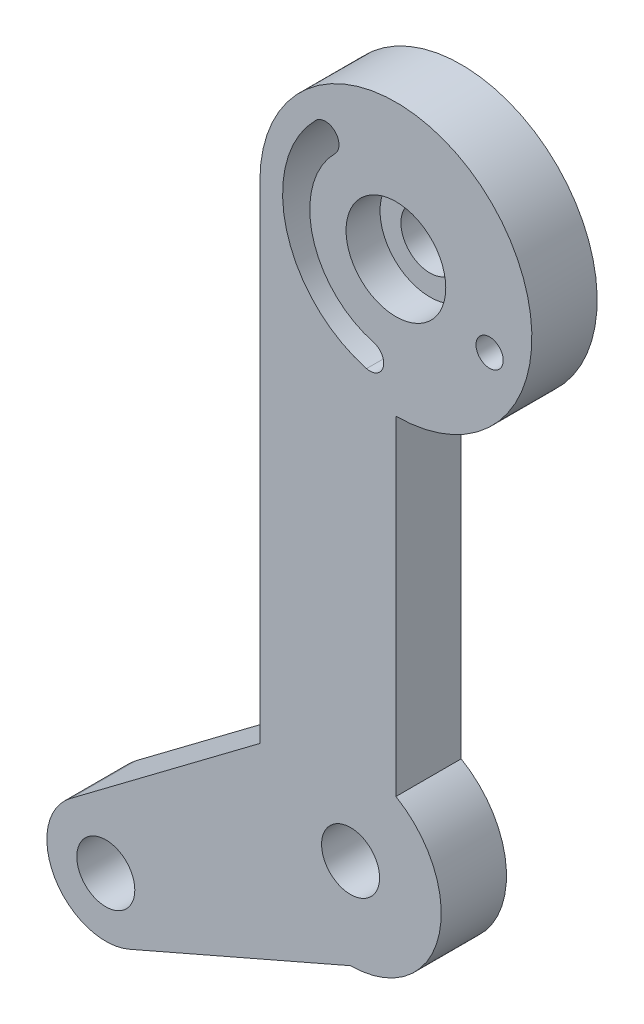
SolidWorks part; units mm, degrees
ref_plane "Front Plane" through (0, 0, 0) normal (0, 0, 1) x (1, 0, 0)
ref_plane "Top Plane" through (0, 0, 0) normal (0, 1, 0) x (1, 0, 0)
ref_plane "Right Plane" through (0, 0, 0) normal (1, 0, 0) x (0, 0, -1)
sketch "Sketch1" plane through (0, 0, 0) normal (0, 0, 1) x (1, 0, 0)
  line L0 (-5, 30) -> (-5, 3.1174)
  line L1 (2.5, 22.5) -> (2.5, 4.3301)
  line L2 (-12.2021, -10.3152) -> (0, -5)
  line L3 (-15.4525, -4.7374) -> (-5, 3.1174)
  circle A0 centre (0, 0) radius 1.6
  arc A1 (0, -5) -> (2.5, 4.3301) centre (0, 0) ccw
  circle A2 centre (-13.5, -7.3356) radius 1.6
  arc A3 (-15.4525, -4.7374) -> (-12.2021, -10.3152) centre (-13.5, -7.3356) ccw
  circle A4 centre (2.5, 30) radius 1.6
  arc A5 (2.5, 22.5) -> (-5, 30) centre (2.5, 30) ccw
  dimension "D1" = 3.2
  dimension "D4" = 5
  dimension "D5" = 3.25
  dimension "D6" = 7.5
  dimension "D7" = 12.2021
  dimension "D8" = 13.5
  dimension "D9" = 15.4525
  dimension "D10" = 22.5
extrude "Boss-Extrude1" add sketch "Sketch1" along normal blind 3.6
sketch "Sketch2" plane through (0, 0, 3.6) normal (0, 0, 1) x (1, 0, 0)
  line L0 (-5, 30) -> (-5, 3.1174) construction
  line L1 (2.5, 30) -> (-1.3891, 33.8891) construction
  line L2 (2.5, 30) -> (1.0765, 24.6874) construction
  line L3 (2.5, 30) -> (8, 30) construction
  line L4 (2.5, 30) -> (7.6683, 28.1189) construction
  circle A0 centre (7.6683, 28.1189) radius 0.75
  arc A1 (-0.8588, 33.3588) -> (-1.9194, 34.4194) centre (-1.3891, 33.8891) ccw
  arc A6 (0.8824, 23.963) -> (1.2706, 25.4119) centre (1.0765, 24.6874) ccw
  arc A7 (-1.9194, 34.4194) -> (0.8824, 23.963) centre (2.5, 30) ccw
  arc A8 (-0.8588, 33.3588) -> (1.2706, 25.4119) centre (2.5, 30) ccw
  dimension "D3" = 1.5
  dimension "D4" = 3.0806
  dimension "D2" = 120
  dimension "D1" = 6.25
  dimension "D5" = 20
extrude "Cut-Extrude1" cut sketch "Sketch2" against normal through all
sketch "Sketch3" plane through (0, 0, 0) normal (0, 0, -1) x (-1, 0, 0)
  circle A0 centre (-2.5, 30) radius 2.75
  dimension "D1" = 5.5
extrude "Cut-Extrude2" [suppressed] cut sketch "Sketch3" against normal blind 1.875
sketch "Sketch4" plane through (0, 0, 3.6) normal (0, 0, 1) x (1, 0, 0)
  circle A0 centre (2.5, 30) radius 2.75
  dimension "D1" = 5.5
extrude "Cut-Extrude3" cut sketch "Sketch4" against normal blind 1.875
